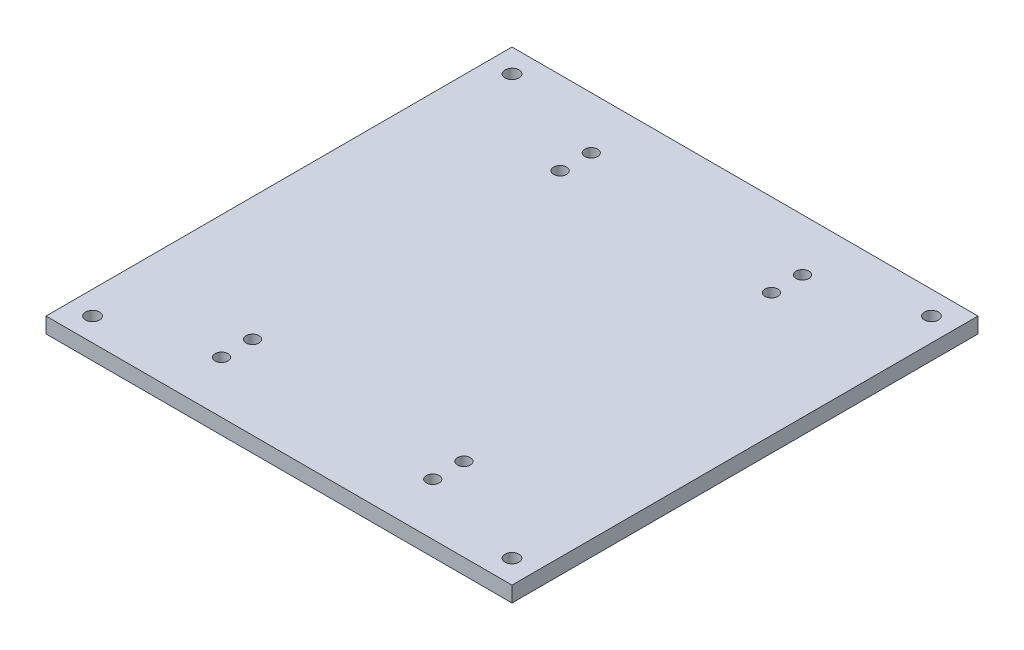
SolidWorks part; units mm, degrees
material "6061-T6 (SS)"
ref_plane "Front Plane" through (0, 0, 0) normal (0, 0, 1) x (1, 0, 0)
ref_plane "Top Plane" through (0, 0, 0) normal (0, 1, 0) x (1, 0, 0)
ref_plane "Right Plane" through (0, 0, 0) normal (1, 0, 0) x (0, 0, -1)
sketch "Sketch1" plane through (0, 0, 0) normal (0, 1, 0) x (1, 0, 0)
  line L0 (-150, 150) -> (150, -150) construction
  line L1 (-150, 150) -> (150, 150)
  line L2 (-150, 150) -> (-150, -150)
  line L3 (-150, -150) -> (150, -150)
  line L4 (150, 150) -> (150, -150)
  dimension "D1" = 300
  dimension "D2" = 300
extrude "Boss-Extrude1" add sketch "Sketch1" along normal blind 10
sketch "Sketch2" plane through (0, 10, 0) normal (0, 1, 0) x (1, 0, 0)
  line L0 (-150, 150) -> (-150, -150) construction
  line L1 (150, 150) -> (-150, 150) construction
  point P0 (0, 0)
  point P4 (-150, 0)
  point P8 (0, 150)
ref_axis "Axis1" through (0, 10, 0) along (0, 1, 0)
hole_wizard "Tapped Hole for M8x1.25 Helicoil1" positions "Sketch3" profile "Sketch4" tap size "M8x1.25" standard "Helicoil® Metric" end condition through all
sketch "Sketch3" plane through (0, 10, 0) normal (0, 1, 0) x (1, 0, 0)
  circle A0 centre (70.5, 116.5) radius 4.5 construction
  circle A1 centre (70.5, 96.5) radius 4.5 construction
  circle A4 centre (-70.5, -116.5) radius 4.5 construction
  circle A7 centre (-70.5, -96.5) radius 4.5 construction
  circle A8 centre (-65.5, 116.5) radius 4.5 construction
  circle A9 centre (-65.5, 96.5) radius 4.5 construction
  circle A10 centre (65.5, -96.5) radius 4.5 construction
  circle A11 centre (65.5, -116.5) radius 4.5 construction
  point P0 (70.5, 116.5)
  point P2 (70.5, 96.5)
  point P4 (65.5, -96.5)
  point P6 (65.5, -116.5)
  point P8 (-65.5, 116.5)
  point P10 (-65.5, 96.5)
  point P12 (-70.5, -96.5)
  point P14 (-70.5, -116.5)
  point P19 (0, 0)
  point P20 (0, 0)
  point P23 (0, 0)
  point P26 (0, 0)
  point P29 (0, 0)
  point P32 (0, 0)
  point P39 (0, 0)
  point P42 (0, 0)
  point P46 (0, 0)
  point P47 (0, 0)
  point P50 (0, 0)
sketch "Sketch4" plane through (70.5, 10, -116.5) normal (1, 0, 0) x (0, 0, 1)
  line L0 (0, 0) -> (0, 10)
  line L1 (0, 10) -> (4.15, 10)
  line L2 (4.15, 10) -> (4.15, 0)
  line L5 (4.15, 0) -> (0, 0)
  line L11 (0, -6.35) -> (0, 107.95) construction
  dimension "Thru Tap Drill Dia." = 8.3
  dimension "Thru Tap Drill Depth" = 10
cosmetic thread "Hole Thread1" parameters "D1"=9.3, "D2"=9.787
cosmetic thread "Hole Thread2" parameters "D1"=9.3, "D2"=9.787
cosmetic thread "Hole Thread3" parameters "D1"=9.3, "D2"=9.787
cosmetic thread "Hole Thread4" parameters "D1"=9.3, "D2"=9.787
cosmetic thread "Hole Thread5" parameters "D1"=9.3, "D2"=9.787
cosmetic thread "Hole Thread6" parameters "D1"=9.3, "D2"=9.787
cosmetic thread "Hole Thread7" parameters "D1"=9.3, "D2"=9.787
cosmetic thread "Hole Thread8" parameters "D1"=9.3, "D2"=9.787
hole_wizard "M8 Clearance Hole2" positions "Sketch5" profile "Sketch6" hole size "M8" standard "ANSI Metric" end condition through all
sketch "Sketch5" plane through (0, 10, 0) normal (0, 1, 0) x (1, 0, 0)
  line L0 (-150, 150) -> (-150, -150) construction
  line L1 (-150, -150) -> (150, -150) construction
  line L2 (-150, 0) -> (150, 0) construction
  line L3 (150, -150) -> (150, 150) construction
  line L5 (0, -150) -> (0, 150) construction
  line L6 (150, 150) -> (-150, 150) construction
  point P6 (-135, -135)
  point P25 (0, 0)
  point P26 (-135, 135)
  point P27 (0, 0)
  point P28 (135, 135)
  point P29 (135, -135)
  dimension "D1" = 15
  dimension "D2" = 15
sketch "Sketch6" plane through (-135, 10, 135) normal (1, 0, 0) x (0, 0, 1)
  line L0 (0, 0) -> (0, 10)
  line L1 (0, 10) -> (4.5, 10)
  line L2 (4.5, 10) -> (4.5, 0)
  line L5 (4.5, 0) -> (0, 0)
  line L11 (0, -6.35) -> (0, 107.95) construction
  dimension "Thru Hole Dia." = 9
  dimension "Thru Hole Depth" = 10
